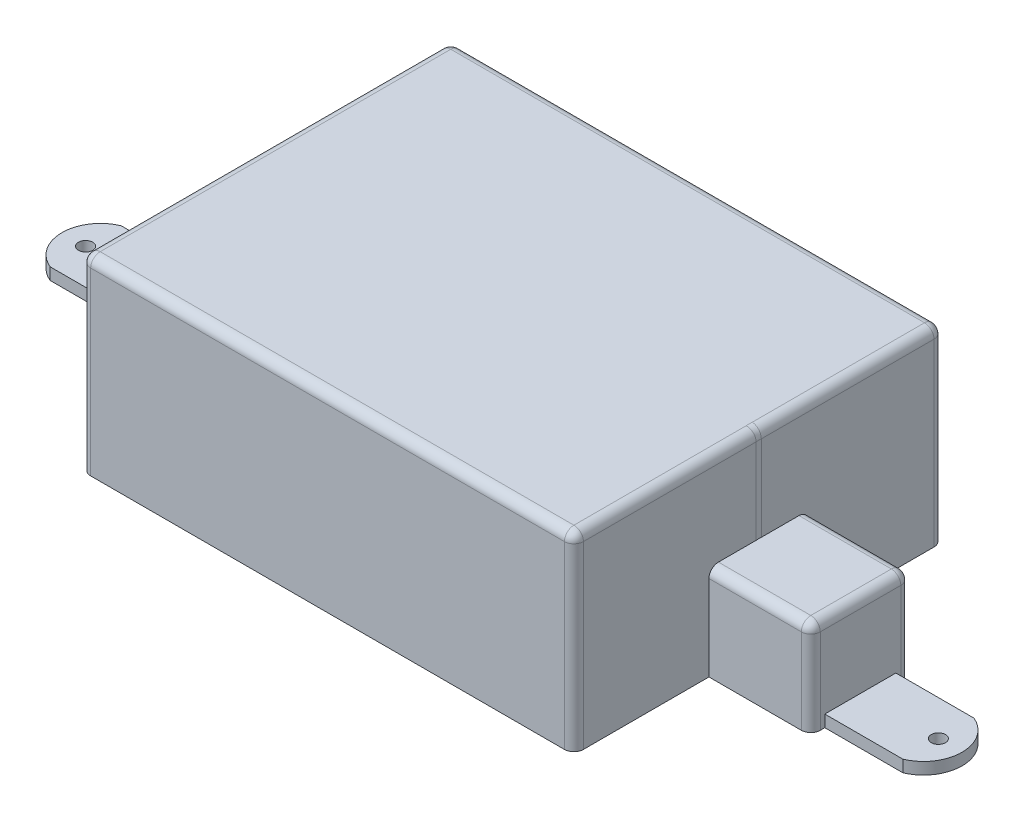
SolidWorks part; units mm, degrees
ref_plane "Front Plane" through (0, 0, 0) normal (0, 0, 1) x (1, 0, 0)
ref_plane "Top Plane" through (0, 0, 0) normal (0, 1, 0) x (1, 0, 0)
ref_plane "Right Plane" through (0, 0, 0) normal (1, 0, 0) x (0, 0, -1)
sketch "Sketch1" plane through (0, 0, 0) normal (0, 1, 0) x (1, 0, 0)
  line L0 (-95, -95) -> (95, -95)
  line L1 (95, -95) -> (95, 95)
  line L2 (95, 95) -> (-95, 95)
  line L3 (-95, 95) -> (-95, -95)
  line L4 (95, 0) -> (-95, 0) construction
  line L5 (95, 0) -> (90, 0)
  line L6 (-95, 0) -> (-90, 0)
  line L7 (0, 26) -> (0, -26) construction
  line L8 (-39, 0) -> (-39, 26) construction
  line L9 (-39, 26) -> (39, 26) construction
  line L10 (39, 26) -> (39, -26) construction
  line L11 (39, -26) -> (-39, -26) construction
  line L12 (-39, -26) -> (-39, 0) construction
  line L13 (-39, 0) -> (39, 0) construction
  line L14 (-67.466, 0) -> (-67.466, 7.5)
  line L15 (-39, 26) -> (-49, 26) construction
  line L16 (-67.466, 7.5) -> (-49, 7.5)
  line L17 (-39, 26) -> (-39, 36) construction
  line L18 (-95, 7.5) -> (-67.466, 7.5)
  line L19 (-49, 7.5) -> (-49, 36)
  line L20 (-49, 36) -> (49, 36)
  line L21 (95, 7.5) -> (67.466, 7.5)
  line L22 (67.466, 7.5) -> (49, 7.5)
  line L23 (49, 7.5) -> (49, 36)
  line L24 (95, -7.5) -> (67.466, -7.5)
  line L25 (67.466, -7.5) -> (49, -7.5)
  line L26 (49, -7.5) -> (49, -36)
  line L27 (-49, -36) -> (49, -36)
  line L28 (-49, -7.5) -> (-49, -36)
  line L29 (-67.466, -7.5) -> (-49, -7.5)
  line L30 (-95, -7.5) -> (-67.466, -7.5)
  line L31 (-67.466, 7.5) -> (-67.466, 10.5) construction
  line L32 (-49, 36) -> (-52, 36) construction
  line L33 (-49, 36) -> (-49, 39) construction
  line L34 (-95, 10.5) -> (-52, 10.5)
  line L35 (-52, 10.5) -> (-52, 39)
  line L36 (-52, 39) -> (52, 39)
  line L37 (95, 10.5) -> (52, 10.5)
  line L38 (52, 10.5) -> (52, 39)
  line L39 (95, -10.5) -> (52, -10.5)
  line L40 (52, -10.5) -> (52, -39)
  line L41 (-52, -39) -> (52, -39)
  line L42 (-52, -10.5) -> (-52, -39)
  line L43 (-95, -10.5) -> (-52, -10.5)
  line L44 (90, -10.5) -> (90, -7.5)
  line L45 (90, 7.5) -> (90, 10.5)
  line L46 (-90, 7.5) -> (-90, 10.5)
  line L47 (-90, -10.5) -> (-90, -7.5)
  line L48 (49, 7.5) -> (49, -7.5)
  line L49 (-49, 7.5) -> (-49, -7.5)
  line L50 (52, -10.5) -> (52, 10.5)
  line L51 (-52, -10.5) -> (-52, 10.5)
  circle A0 centre (90, 0) radius 1.5
  circle A1 centre (-90, 0) radius 1.5
  circle A2 centre (39, 0) radius 1.5
  circle A3 centre (-39, 0) radius 1.5
  circle A4 centre (56.9701, 0) radius 5
  arc A5 (-90, 7.5) -> (-90, -7.5) centre (-86.875, 0) ccw
  arc A6 (90, 7.5) -> (90, -7.5) centre (86.875, 0) cw
  point P34 (0, 36)
  point P52 (0, 39)
  dimension "D1" = 190
  dimension "D2" = 190
extrude "Boss-Extrude1" add sketch "Sketch1" along normal blind 40 contours L19 L49 L28 L27 L26 L48 L23 L20 A2 A3 | L51 L16 L19 L20 L23 L22 L50 L38 L36 L35 | L50 A4 L22 L48 L25 | L51 L42 L41 L40 L50 L25 L26 L27 L28 L29 | L51 L29 L49 L16 | A2 | A3 region at (-50.9133, 0, 9) region at (-50.5, 0, 0) region at (50.4993, 0, 0) region at (0, 0, 0) region at (-50.9133, 0, -9) region at (39, 0, 0) region at (-39, 0, 0)
sketch "Sketch2" plane through (0, 0, 0) normal (0, -1, 0) x (1, 0, 0)
  line L0 (-95, -95) -> (95, -95)
  line L1 (95, -95) -> (95, 95)
  line L2 (95, 95) -> (-95, 95)
  line L3 (-95, 95) -> (-95, -95)
  line L4 (95, 0) -> (-95, 0) construction
  line L5 (95, 0) -> (90, 0)
  line L6 (-95, 0) -> (-90, 0)
  line L7 (0, 26) -> (0, -26) construction
  line L8 (-39, 0) -> (-39, 26) construction
  line L9 (-39, 26) -> (39, 26) construction
  line L10 (39, 26) -> (39, -26) construction
  line L11 (39, -26) -> (-39, -26) construction
  line L12 (-39, -26) -> (-39, 0) construction
  line L13 (-39, 0) -> (39, 0) construction
  line L14 (-67.466, 0) -> (-67.466, 7.5)
  line L15 (-39, 26) -> (-49, 26) construction
  line L16 (-67.466, 7.5) -> (-49, 7.5)
  line L17 (-39, 26) -> (-39, 36) construction
  line L18 (-95, 7.5) -> (-67.466, 7.5)
  line L19 (-49, 7.5) -> (-49, 36)
  line L20 (-49, 36) -> (49, 36)
  line L21 (95, 7.5) -> (67.466, 7.5)
  line L22 (67.466, 7.5) -> (49, 7.5)
  line L23 (49, 7.5) -> (49, 36)
  line L24 (95, -7.5) -> (67.466, -7.5)
  line L25 (67.466, -7.5) -> (49, -7.5)
  line L26 (49, -7.5) -> (49, -36)
  line L27 (-49, -36) -> (49, -36)
  line L28 (-49, -7.5) -> (-49, -36)
  line L29 (-67.466, -7.5) -> (-49, -7.5)
  line L30 (-95, -7.5) -> (-67.466, -7.5)
  line L31 (-67.466, 7.5) -> (-67.466, 10.5) construction
  line L32 (-49, 36) -> (-52, 36) construction
  line L33 (-49, 36) -> (-49, 39) construction
  line L34 (-95, 10.5) -> (-52, 10.5)
  line L35 (-52, 10.5) -> (-52, 39)
  line L36 (-52, 39) -> (52, 39)
  line L37 (95, 10.5) -> (52, 10.5)
  line L38 (52, 10.5) -> (52, 39)
  line L39 (95, -10.5) -> (52, -10.5)
  line L40 (52, -10.5) -> (52, -39)
  line L41 (-52, -39) -> (52, -39)
  line L42 (-52, -10.5) -> (-52, -39)
  line L43 (-95, -10.5) -> (-52, -10.5)
  line L44 (90, -10.5) -> (90, -7.5)
  line L45 (90, 7.5) -> (90, 10.5)
  line L46 (-90, 7.5) -> (-90, 10.5)
  line L47 (-90, -10.5) -> (-90, -7.5)
  line L48 (73.5, 10.5) -> (73.5, -10.5)
  circle A0 centre (90, 0) radius 1.5
  circle A1 centre (-90, 0) radius 1.5
  circle A2 centre (39, 0) radius 1.5
  circle A3 centre (-39, 0) radius 1.5
  circle A4 centre (56.9701, 0) radius 5
  arc A5 (-90, 7.5) -> (-90, -7.5) centre (-86.875, 0) ccw
  arc A6 (90, 7.5) -> (90, -7.5) centre (86.875, 0) cw
  point P34 (0, 36)
  point P52 (0, 39)
  line M8 (52, -39) -> (52, -0.5461)
  arc M9 (52, -0.5461) -> (52, 0.5461) centre (56.9701, 0) cw
  line M10 (52, 0.5461) -> (52, 39)
  dimension "D1" = 190
  dimension "D2" = 190
extrude "Boss-Extrude4" add sketch "Sketch2" against normal blind 20 contours A4 L25 L24 L48 L21 L22 M10 M8 | L48 L24 L25 L39 M8 | A4 M9 region at (62.75, 0, -9) region at (64.6096, 0, 0) region at (56.9701, 0, 0)
sketch "Sketch3" plane through (0, 0, 0) normal (0, -1, 0) x (1, 0, 0)
  line L0 (-95, -95) -> (95, -95)
  line L1 (95, -95) -> (95, 95)
  line L2 (95, 95) -> (-95, 95)
  line L3 (-95, 95) -> (-95, -95)
  line L4 (95, 0) -> (-95, 0) construction
  line L5 (95, 0) -> (90, 0)
  line L6 (-95, 0) -> (-90, 0)
  line L7 (0, 26) -> (0, -26) construction
  line L8 (-39, 0) -> (-39, 26) construction
  line L9 (-39, 26) -> (39, 26) construction
  line L10 (39, 26) -> (39, -26) construction
  line L11 (39, -26) -> (-39, -26) construction
  line L12 (-39, -26) -> (-39, 0) construction
  line L13 (-39, 0) -> (39, 0) construction
  line L14 (-67.466, 0) -> (-67.466, 7.5)
  line L15 (-39, 26) -> (-49, 26) construction
  line L16 (-67.466, 7.5) -> (-49, 7.5)
  line L17 (-39, 26) -> (-39, 36) construction
  line L18 (-95, 7.5) -> (-67.466, 7.5)
  line L19 (-49, 7.5) -> (-49, 36)
  line L20 (-49, 36) -> (49, 36)
  line L21 (95, 7.5) -> (67.466, 7.5)
  line L22 (67.466, 7.5) -> (49, 7.5)
  line L23 (49, 7.5) -> (49, 36)
  line L24 (95, -7.5) -> (67.466, -7.5)
  line L25 (67.466, -7.5) -> (49, -7.5)
  line L26 (49, -7.5) -> (49, -36)
  line L27 (-49, -36) -> (49, -36)
  line L28 (-49, -7.5) -> (-49, -36)
  line L29 (-67.466, -7.5) -> (-49, -7.5)
  line L30 (-95, -7.5) -> (-67.466, -7.5)
  line L31 (-67.466, 7.5) -> (-67.466, 10.5) construction
  line L32 (-49, 36) -> (-52, 36) construction
  line L33 (-49, 36) -> (-49, 39) construction
  line L34 (-95, 10.5) -> (-52, 10.5)
  line L35 (-52, 10.5) -> (-52, 39)
  line L36 (-52, 39) -> (52, 39)
  line L37 (95, 10.5) -> (52, 10.5)
  line L38 (52, 10.5) -> (52, 39)
  line L39 (95, -10.5) -> (52, -10.5)
  line L40 (52, -10.5) -> (52, -39)
  line L41 (-52, -39) -> (52, -39)
  line L42 (-52, -10.5) -> (-52, -39)
  line L43 (-95, -10.5) -> (-52, -10.5)
  line L44 (90, -10.5) -> (90, -7.5)
  line L45 (90, 7.5) -> (90, 10.5)
  line L46 (-90, 7.5) -> (-90, 10.5)
  line L47 (-90, -10.5) -> (-90, -7.5)
  line L48 (73.5, 7.5) -> (73.5, 10.5)
  line L49 (73.5, 10.5) -> (73.5, -10.5)
  line L50 (-67.466, 0) -> (-67.466, -10.5)
  line L51 (-49, 7.5) -> (-49, -7.5)
  line L52 (49, 7.5) -> (49, -7.5)
  circle A0 centre (90, 0) radius 1.5
  circle A1 centre (-90, 0) radius 1.5
  circle A2 centre (39, 0) radius 1.5
  circle A3 centre (-39, 0) radius 1.5
  circle A4 centre (56.9701, 0) radius 5
  arc A5 (-90, 7.5) -> (-90, -7.5) centre (-86.875, 0) ccw
  arc A6 (90, 7.5) -> (90, -7.5) centre (86.875, 0) cw
  point P34 (0, 36)
  point P52 (0, 39)
  dimension "D1" = 190
  dimension "D2" = 190
extrude "Cut-Extrude1" cut sketch "Sketch3" against normal blind 37 contours L52 L23 L20 L19 L51 L28 L27 L26 A2 A3 | A3 | A2 region at (0, 0, 0) region at (39, 0, 0) region at (-39, 0, 0)
sketch "Sketch4" plane through (0, 0, 0) normal (0, -1, 0) x (1, 0, 0)
  line L0 (-95.0236, -94.9521) -> (94.9764, -94.9521)
  line L1 (94.9764, -94.9521) -> (94.9764, 95.0479)
  line L2 (94.9764, 95.0479) -> (-95.0236, 95.0479)
  line L3 (-95.0236, 95.0479) -> (-95.0236, -94.9521)
  line L4 (94.9764, 0.0479) -> (-95.0236, 0.0479) construction
  line L5 (94.9764, 0.0479) -> (89.9764, 0.0479)
  line L6 (-95.0236, 0.0479) -> (-90.0236, 0.0479)
  line L7 (-0.0236, 26.0479) -> (-0.0236, -25.9521) construction
  line L8 (-39.0236, 0.0479) -> (-39.0236, 26.0479) construction
  line L9 (-39.0236, 26.0479) -> (38.9764, 26.0479) construction
  line L10 (38.9764, 26.0479) -> (38.9764, -25.9521) construction
  line L11 (38.9764, -25.9521) -> (-39.0236, -25.9521) construction
  line L12 (-39.0236, -25.9521) -> (-39.0236, 0.0479) construction
  line L13 (-39.0236, 0.0479) -> (38.9764, 0.0479) construction
  line L14 (-67.4897, 0.0479) -> (-67.4897, 7.5479)
  line L15 (-39.0236, 26.0479) -> (-49.0236, 26.0479) construction
  line L16 (-67.4897, 7.5479) -> (-49.0236, 7.5479)
  line L17 (-39.0236, 26.0479) -> (-39.0236, 36.0479) construction
  line L18 (-95.0236, 7.5479) -> (-67.4897, 7.5479)
  line L19 (-49.0236, 7.5479) -> (-49.0236, 36.0479)
  line L20 (-49.0236, 36.0479) -> (48.9764, 36.0479)
  line L21 (94.9764, 7.5479) -> (67.4424, 7.5479)
  line L22 (67.4424, 7.5479) -> (48.9764, 7.5479)
  line L23 (48.9764, 7.5479) -> (48.9764, 36.0479)
  line L24 (94.9764, -7.4521) -> (67.4424, -7.4521)
  line L25 (67.4424, -7.4521) -> (48.9764, -7.4521)
  line L26 (48.9764, -7.4521) -> (48.9764, -35.9521)
  line L27 (-49.0236, -35.9521) -> (48.9764, -35.9521)
  line L28 (-49.0236, -7.4521) -> (-49.0236, -35.9521)
  line L29 (-67.4897, -7.4521) -> (-49.0236, -7.4521)
  line L30 (-95.0236, -7.4521) -> (-67.4897, -7.4521)
  line L31 (-67.4897, 7.5479) -> (-67.4897, 10.5479) construction
  line L32 (-49.0236, 36.0479) -> (-52.0236, 36.0479) construction
  line L33 (-49.0236, 36.0479) -> (-49.0236, 39.0479) construction
  line L34 (-95.0236, 10.5479) -> (-52.0236, 10.5479)
  line L35 (-52.0236, 10.5479) -> (-52.0236, 39.0479)
  line L36 (-52.0236, 39.0479) -> (51.9764, 39.0479)
  line L37 (94.9764, 10.5479) -> (51.9764, 10.5479)
  line L38 (51.9764, 10.5479) -> (51.9764, 39.0479)
  line L39 (94.9764, -10.4521) -> (51.9764, -10.4521)
  line L40 (51.9764, -10.4521) -> (51.9764, -38.9521)
  line L41 (-52.0236, -38.9521) -> (51.9764, -38.9521)
  line L42 (-52.0236, -10.4521) -> (-52.0236, -38.9521)
  line L43 (-95.0236, -10.4521) -> (-52.0236, -10.4521)
  line L44 (89.9764, -10.4521) -> (89.9764, -7.4521)
  line L45 (89.9764, 7.5479) -> (89.9764, 10.5479)
  line L46 (-90.0236, 7.5479) -> (-90.0236, 10.5479)
  line L47 (-90.0236, -10.4521) -> (-90.0236, -7.4521)
  line L48 (73.4764, 7.5479) -> (73.4764, 10.5479)
  line L49 (73.4764, 10.5479) -> (73.4764, -10.4521)
  line L50 (-67.4897, 0.0479) -> (-67.4897, -10.4521)
  line L51 (-49.0236, 7.5479) -> (-49.0236, -7.4521)
  line L52 (48.9764, 7.5479) -> (48.9764, -7.4521)
  circle A0 centre (89.9764, 0.0479) radius 1.5
  circle A1 centre (-90.0236, 0.0479) radius 1.5
  circle A2 centre (38.9764, 0.0479) radius 1.5
  circle A3 centre (-39.0236, 0.0479) radius 1.5
  circle A4 centre (56.9464, 0.0479) radius 5
  arc A5 (-90.0236, 7.5479) -> (-90.0236, -7.4521) centre (-86.8986, 0.0479) ccw
  arc A6 (89.9764, 7.5479) -> (89.9764, -7.4521) centre (86.8514, 0.0479) cw
  point P34 (-0.0236, 36.0479)
  point P52 (-0.0236, 39.0479)
  line M6 (73.5, 7.5) -> (52, 7.5)
  line M9 (-52, 39) -> (-52, -39)
  line M13 (73.5, -10.5) -> (73.5, 7.5)
  dimension "D1" = 190
  dimension "D2" = 190
extrude "Boss-Extrude5" add sketch "Sketch4" against normal blind 2.5 contours A6 L21 L49 L24 A0 M6 M13 | L14 L50 L29 L16 M9 | L18 A5 A1 L30 L50 L14 region at (-80.4259, 0, 0.0479) region at (83.4377, 0, 0.048) region at (-59.7448, 0, 0.0479)
sketch "Sketch5" plane through (73.5, 0, 0) normal (1, 0, 0) x (0, 0, -1)
sketch "Sketch6" plane through (0, 0, 0) normal (0, -1, 0) x (1, 0, 0)
  line L0 (52, -10.5) -> (73.5, -10.5)
  line L1 (73.5, -10.5) -> (73.5, -7.4521)
  line L2 (52, 10.5) -> (52, 7.5)
  line L5 (73.5, 10.5) -> (73.5, 7.4521)
  line L6 (52, 10.5) -> (73.5, 10.5)
  line L7 (52, 7.5) -> (73.5, 7.4521)
  line M4 (73.4764, 7.5479) -> (73.4764, 7.5)
  line M5 (73.4764, 7.5) -> (52, 7.5)
  line M6 (52, 7.5) -> (52, 39)
  line M19 (89.9764, 7.5479) -> (73.4764, 7.5479)
extrude "Boss-Extrude6" add sketch "Sketch6" against normal blind 20 contours L6 L5 M6 M5 M4 M19 region at (62.7498, 0, 9)
sketch "Sketch7" plane through (73.4764, 0, 0) normal (1, 0, 0) x (0, 0, -1)
  line L0 (-7.5479, 20) -> (-7.5, 20)
  line L1 (-7.5, 20) -> (-7.5, 2.5)
  line L2 (-7.5, 2.5) -> (-7.5479, 2.5)
  line L3 (-7.5479, 2.5) -> (-7.5479, 20)
extrude "Boss-Extrude7" add sketch "Sketch7" along normal blind 0.0236
sketch "Sketch8" plane through (73.5, 0, 0) normal (1, 0, 0) x (0, 0, -1)
  line L0 (-10.5, 0) -> (-10.5, 20)
  line L1 (-10.5, 20) -> (10.5, 20)
  line L2 (10.5, 20) -> (10.5, 0)
  line L3 (10.5, 0) -> (-10.5, 0)
  line L4 (-8.5, 18) -> (-8.5, 2.5)
  line L5 (-8.5, 2.5) -> (8.5, 2.5)
  line L6 (8.5, 2.5) -> (8.5, 18)
  line L7 (8.5, 18) -> (-8.5, 18)
  point P10 (10.5, 20)
  dimension "D1" = 2
  dimension "D2" = 21
  dimension "D3" = 2
  dimension "D4" = 20
  dimension "D5" = 2
sketch "Sketch9" plane through (49, 0, 0) normal (-1, 0, 0) x (0, 0, 1)
  line L0 (-10.5, 20) -> (-10.5, 0)
  line L1 (-10.5, 0) -> (10.5, 0)
  line L2 (10.5, 0) -> (10.5, 20)
  line L3 (10.5, 20) -> (-10.5, 20)
  line L4 (-8.5, 18) -> (8.5, 18)
  line L5 (8.5, 18) -> (8.5, 2.5)
  line L6 (8.5, 2.5) -> (-8.5, 2.5)
  line L7 (-8.5, 2.5) -> (-8.5, 18)
  line L8 (-8.5, 2.5) -> (-8.5, 0)
  line L9 (8.5, 2.5) -> (8.5, 0)
  line L10 (-8.5, 0) -> (8.5, 0)
  dimension "D1" = 2.5
extrude "Cut-Extrude2" cut sketch "Sketch9" against normal blind 22.5 contours L7 L4 L5 L6
sketch "Sketch11" plane through (0, 0, 0) normal (0, -1, 0) x (1, 0, 0)
  line L0 (-95, -95) -> (95, -95)
  line L1 (95, -95) -> (95, 95)
  line L2 (95, 95) -> (-95, 95)
  line L3 (-95, 95) -> (-95, -95)
  line L4 (95, 0) -> (-95, 0) construction
  line L5 (95, 0) -> (90, 0)
  line L6 (-95, 0) -> (-90, 0)
  line L7 (0, 26) -> (0, -26) construction
  line L8 (-39, 0) -> (-39, 26) construction
  line L9 (-39, 26) -> (39, 26) construction
  line L10 (39, 26) -> (39, -26) construction
  line L11 (39, -26) -> (-39, -26) construction
  line L12 (-39, -26) -> (-39, 0) construction
  line L13 (-39, 0) -> (39, 0) construction
  line L14 (-67.466, 0) -> (-67.466, 7.5)
  line L15 (-39, 26) -> (-49, 26) construction
  line L16 (-67.466, 7.5) -> (-49, 7.5)
  line L17 (-39, 26) -> (-39, 36) construction
  line L18 (-95, 7.5) -> (-67.466, 7.5)
  line L19 (-49, 7.5) -> (-49, 36)
  line L20 (-49, 36) -> (49, 36)
  line L21 (95, 7.5) -> (67.466, 7.5)
  line L22 (67.466, 7.5) -> (49, 7.5)
  line L23 (49, 7.5) -> (49, 36)
  line L24 (95, -7.5) -> (67.466, -7.5)
  line L25 (67.466, -7.5) -> (49, -7.5)
  line L26 (49, -7.5) -> (49, -36)
  line L27 (-49, -36) -> (49, -36)
  line L28 (-49, -7.5) -> (-49, -36)
  line L29 (-67.466, -7.5) -> (-49, -7.5)
  line L30 (-95, -7.5) -> (-67.466, -7.5)
  line L31 (-67.466, 7.5) -> (-67.466, 10.5) construction
  line L32 (-49, 36) -> (-52, 36) construction
  line L33 (-49, 36) -> (-49, 39) construction
  line L34 (-95, 10.5) -> (-52, 10.5)
  line L35 (-52, 10.5) -> (-52, 39)
  line L36 (-52, 39) -> (52, 39)
  line L37 (95, 10.5) -> (52, 10.5)
  line L38 (52, 10.5) -> (52, 39)
  line L39 (95, -10.5) -> (52, -10.5)
  line L40 (52, -10.5) -> (52, -39)
  line L41 (-52, -39) -> (52, -39)
  line L42 (-52, -10.5) -> (-52, -39)
  line L43 (-95, -10.5) -> (-52, -10.5)
  line L44 (90, -10.5) -> (90, -7.5)
  line L45 (90, 7.5) -> (90, 10.5)
  line L46 (-90, 7.5) -> (-90, 10.5)
  line L47 (-90, -10.5) -> (-90, -7.5)
  line L48 (49, 7.5) -> (49, -7.5)
  line L49 (-49, 7.5) -> (-49, -7.5)
  line L50 (52, -10.5) -> (52, 10.5)
  line L51 (-52, -10.5) -> (-52, 10.5)
  circle A0 centre (90, 0) radius 1.5
  circle A1 centre (-90, 0) radius 1.5
  circle A2 centre (39, 0) radius 1.5
  circle A3 centre (-39, 0) radius 1.5
  circle A4 centre (56.9701, 0) radius 5
  arc A5 (-90, 7.5) -> (-90, -7.5) centre (-86.875, 0) ccw
  arc A6 (90, 7.5) -> (90, -7.5) centre (86.875, 0) cw
  point P34 (0, 36)
  point P52 (0, 39)
  dimension "D1" = 190
  dimension "D2" = 190
extrude "Cut-Extrude3" cut sketch "Sketch11" against normal blind 13.5 contours A4 L50 region at (56.9715, 0, 0)
sketch "Sketch13" plane through (49, 0, 0) normal (-1, 0, 0) x (0, 0, 1)
  line L0 (-8.5, 2.5) -> (-8.5, 0)
  line L1 (36, 0) -> (-36, 0) construction
  line L2 (8.5, 2.5) -> (8.5, 0)
  line L3 (8.5, 0) -> (-8.5, 0)
  line L4 (8.5, 2.5) -> (-8.5, 2.5)
extrude "Cut-Extrude4" cut sketch "Sketch13" against normal blind 22.5
fillet "Fillet1" radius 2 6 edges at (73.5, 10, -10.5) (73.5, 10, 10.5) (-52, 20, -39) (52, 20, -39) (-52, 20, 39) (52, 20, 39)
fillet "Fillet2" radius 2 10 edges at (51.4142, 40, -38.4142) (-51.4142, 40, -38.4142) (-51.4142, 40, 38.4142) (51.4142, 40, 38.4142) (51.9701, 40, 0) (52, 40, -18.7731) (52, 40, 18.7731) (0, 40, -39) (-52, 40, 0) (0, 40, 39)
fillet "Fillet3" radius 2 5 edges at (72.9142, 20, -9.9142) (72.9142, 20, 9.9142) (61.75, 20, -10.5) (73.5, 20, 0) (61.75, 20, 10.5)
